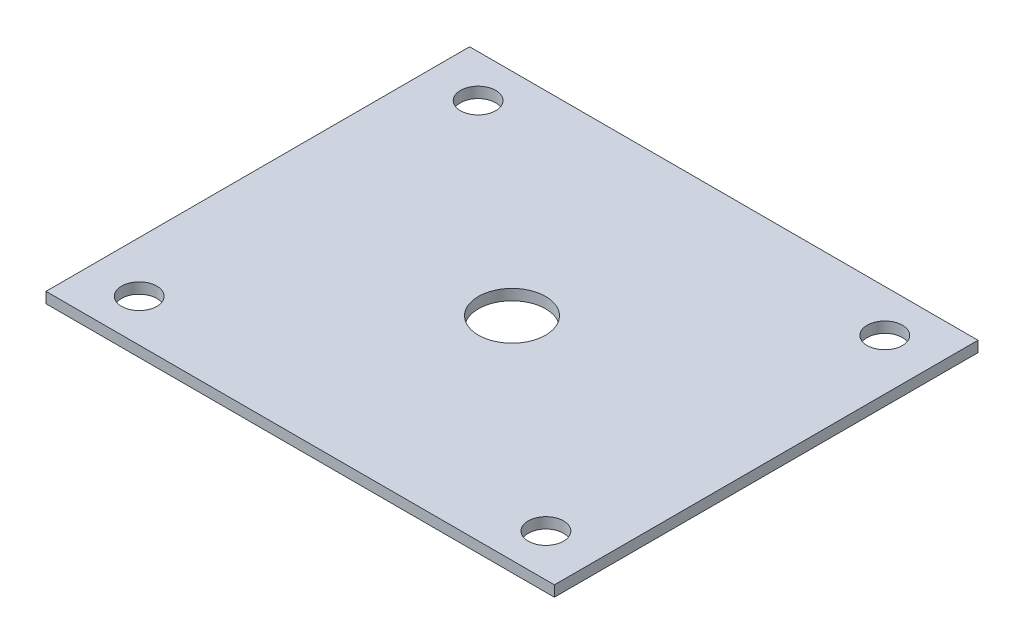
SolidWorks part; units mm, degrees
ref_plane "Front Plane" through (0, 0, 0) normal (0, 0, 1) x (1, 0, 0)
ref_plane "Top Plane" through (0, 0, 0) normal (0, 1, 0) x (1, 0, 0)
ref_plane "Right Plane" through (0, 0, 0) normal (1, 0, 0) x (0, 0, -1)
sketch "Sketch1" plane through (0, 0, 0) normal (0, 1, 0) x (1, 0, 0)
  line L0 (30, 25) -> (0, 25) construction
  line L1 (-37.5, -31.25) -> (37.5, -31.25)
  line L2 (-37.5, -31.25) -> (-37.5, 31.25)
  line L3 (-37.5, 31.25) -> (37.5, 31.25)
  line L4 (37.5, -31.25) -> (37.5, 31.25)
  line L5 (-37.5, -31.25) -> (37.5, 31.25) construction
  line L6 (-37.5, 31.25) -> (37.5, -31.25) construction
  line L7 (0, 25) -> (0, 0) construction
  line L8 (-37.5, 0) -> (37.5, 0) construction
  circle A0 centre (0, 0) radius 4.955
  circle A1 centre (30, 25) radius 2.6
  circle A2 centre (-30, 25) radius 2.6
  circle A3 centre (-30, -25) radius 2.6
  circle A4 centre (30, -25) radius 2.6
  point P0 (0, 0)
  dimension "D3" = 9.91
  dimension "D6" = 5.2
  dimension "D1" = 62.5
  dimension "D2" = 75
  dimension "D4" = 30
  dimension "D5" = 25
extrude "Boss-Extrude1" add sketch "Sketch1" along normal blind 0.7937 and the other way blind 0.7937
